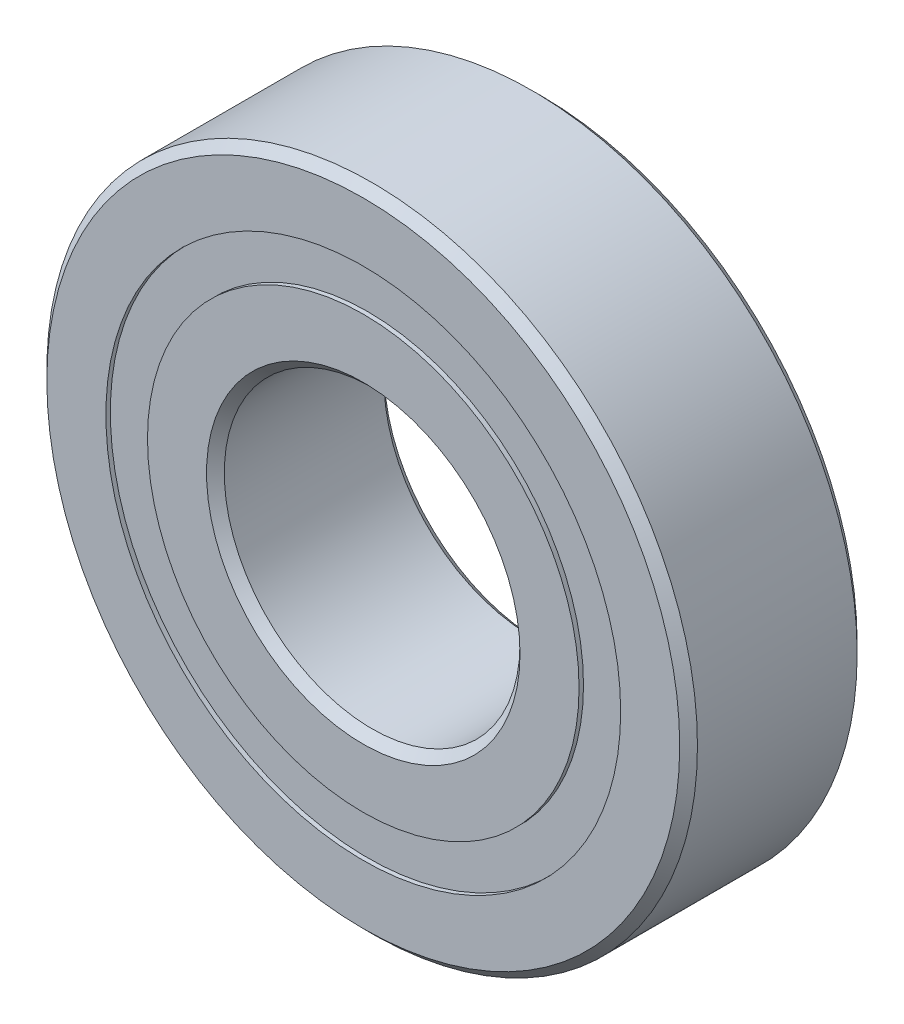
SolidWorks part; units mm, degrees
material "Alloy Steel"
ref_plane "Front Plane" through (0, 0, 0) normal (0, 0, 1) x (1, 0, 0)
ref_plane "Top Plane" through (0, 0, 0) normal (0, 1, 0) x (1, 0, 0)
ref_plane "Right Plane" through (0, 0, 0) normal (1, 0, 0) x (0, 0, -1)
sketch "Sketch1" plane through (0, 0, 0) normal (1, 0, 0) x (0, 0, -1)
  line L0 (-3, 0) -> (3, 0) construction
  line L1 (0, 11) -> (0, -11) construction
  line L2 (2.7, 11) -> (-2.7, 11)
  line L3 (-2.7, 11) -> (-3, 10.7)
  line L4 (-3, 10.7) -> (-3, 8.7033)
  line L5 (-3, 8.7033) -> (-1.3333, 8.7033)
  line L6 (3, 8.7033) -> (1.3333, 8.7033)
  line L7 (3, 10.7) -> (3, 8.7033)
  line L8 (2.7, 11) -> (3, 10.7)
  line L9 (0, 11) -> (0, 8) construction
  line L10 (0, 8) -> (0, 5) construction
  arc A0 (-1.3333, 8.7033) -> (1.3333, 8.7033) centre (0, 8) cw
  point P14 (0, 5)
  dimension "D3" = 2.6667
  dimension "D1" = 45
  dimension "Width" = 6
  dimension "OD" = 22
  dimension "D2" = 0.3
  dimension "Shaft Dia" = 10
  dimension "D4" = 0.7033
revolve "Revolve1" add sketch "Sketch1" angle 360 about L0
sketch "Sketch3" plane through (0, 0, 0) normal (1, 0, 0) x (0, 0, -1)
  line L0 (-3, 7.2967) -> (-1.3333, 7.2967)
  line L1 (0, 11) -> (0, -11) construction
  line L2 (-3, 10.7) -> (-3, 8.7033) construction
  line L3 (-3, 7.2967) -> (-3, 5.3)
  line L4 (-2.7, 11) -> (-3, 10.7) construction
  line L5 (-3, 5.3) -> (-2.7, 5)
  line L6 (-2.7, 5) -> (2.7, 5)
  line L7 (2.7, 11) -> (2.7, -11) construction
  line L8 (2.7, 5) -> (3, 5.3)
  line L9 (3, -10.7) -> (3, 10.7) construction
  line L10 (3, 5.3) -> (3, 7.2967)
  line L11 (3, 7.2967) -> (1.3333, 7.2967)
  line L13 (2.7, 11) -> (3, 10.7) construction
  arc A0 (1.3333, 8.7033) -> (-1.3333, 8.7033) centre (0, 8) ccw construction
  arc A1 (1.3333, 7.2967) -> (-1.3333, 7.2967) centre (0, 8) cw
revolve "Revolve3" add sketch "Sketch3" angle 360 about L0
sketch "Sketch4" plane through (0, 0, 0) normal (1, 0, 0) x (0, 0, -1)
  line L0 (-1.5074, 8) -> (1.5074, 8)
  arc A2 (-1.5074, 8) -> (1.5074, 8) centre (0, 8) cw
  arc A3 (1.3333, 8.7033) -> (-1.3333, 8.7033) centre (0, 8) ccw construction
revolve "Revolve4" add sketch "Sketch4" angle 360 about L0
ref_axis "Axis1" through (0, 0, -3) along (0, 0, 1)
pattern_circular "CirPattern1" count 12 every 30 about axis through (0, 0, -3) along (0, 0, 1) of bodies 104
sketch "Sketch5" plane through (0, 0, 0) normal (1, 0, 0) x (0, 0, -1)
  line L0 (-3, 8.7033) -> (-1.3333, 8.7033) construction
  line L1 (-2.85, 8.7033) -> (-1.5074, 8.7033)
  line L2 (-2.85, 8.7033) -> (-2.85, 7.2967)
  line L3 (-2.85, 7.2967) -> (-1.5074, 7.2967)
  line L4 (-1.5074, 8.7033) -> (-1.5074, 7.2967)
  line L5 (-3, 7.2967) -> (-1.3333, 7.2967) construction
  line L6 (3, 8.7033) -> (1.3333, 8.7033) construction
  line L7 (2.85, 8.7033) -> (1.5074, 8.7033)
  line L8 (2.85, 8.7033) -> (2.85, 7.2967)
  line L9 (2.85, 7.2967) -> (1.5074, 7.2967)
  line L10 (1.5074, 8.7033) -> (1.5074, 7.2967)
  line L11 (3, 7.2967) -> (1.3333, 7.2967) construction
  line L12 (-2.7, 11) -> (-3, 10.7) construction
  point P18 (-2.85, 10.85)
revolve "Revolve5" add sketch "Sketch5" angle 360 about L0
equation "\"D2@Sketch1\" = \"Width@Sketch1\"*.05"
equation "\"D3@Sketch1\" = \"Width@Sketch1\"/2.25"
equation "\"D4@Sketch1\" = (((\"OD@Sketch1\"-\"Width@Sketch1\")/2)/3.25)/3.5"
equation "\"D2@CirPattern1\" = 360/\"Balls@CirPattern1\""
